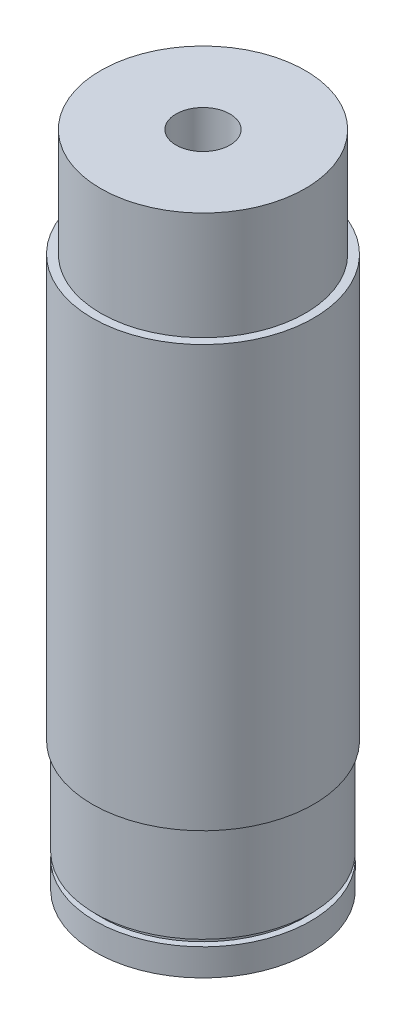
SolidWorks part; units mm, degrees
material "ABS"
ref_plane "Plan de face" through (0, 0, 0) normal (0, 0, 1) x (1, 0, 0)
ref_plane "Plan de dessus" through (0, 0, 0) normal (0, 1, 0) x (1, 0, 0)
ref_plane "Plan de droite" through (0, 0, 0) normal (1, 0, 0) x (0, 0, -1)
sketch "Esquisse1" plane through (0, 0, 0) normal (0, 1, 0) x (1, 0, 0)
  circle A0 centre (0, 0) radius 20.5
  dimension "D1" = 41
extrude "Boss.-Extru.1" add sketch "Esquisse1" along normal blind 122
sketch "Esquisse2" plane through (0, 122, 0) normal (0, 1, 0) x (1, 0, 0)
  circle A0 centre (0, 0) radius 18.95
  dimension "D1" = 37.9
extrude "Enlèv. mat.-Extru.1" cut sketch "Esquisse2" against normal blind 20 flip side to cut
sketch "Esquisse3" plane through (0, 0, 0) normal (0, -1, 0) x (1, 0, 0)
  circle A0 centre (0, 0) radius 19.95
  dimension "D1" = 39.9
extrude "Enlèv. mat.-Extru.2" cut sketch "Esquisse3" against normal blind 24 flip side to cut
sketch "Esquisse4" plane through (0, 0, 0) normal (0, 0, 1) x (1, 0, 0)
  line L0 (-19.95, 24) -> (-19.95, 0) construction
  line L1 (-21.1, 6.2) -> (-18.8, 6.2)
  line L2 (-21.1, 6.2) -> (-21.1, 5)
  line L3 (-21.1, 5) -> (-18.8, 5)
  line L4 (-18.8, 6.2) -> (-18.8, 5)
  line L5 (-21.1, 6.2) -> (-18.8, 5) construction
  line L6 (-21.1, 5) -> (-18.8, 6.2) construction
  line L7 (-19.95, 0) -> (19.95, 0) construction
  line L8 (0, 0) -> (0, 8.7803) construction
  point P0 (-19.95, 5.6)
  point P12 (0, 8.7803)
  dimension "D1" = 1.2
  dimension "D2" = 18.8
  dimension "D3" = 5
revolve "Enlèvement de matière-Révolution1" cut sketch "Esquisse4" angle 360 about L8
sketch "Esquisse5" plane through (0, 122, 0) normal (0, 1, 0) x (1, 0, 0)
  circle A0 centre (0, 0) radius 5
  dimension "D1" = 10
extrude "Enlèv. mat.-Extru.3" cut sketch "Esquisse5" against normal through all
